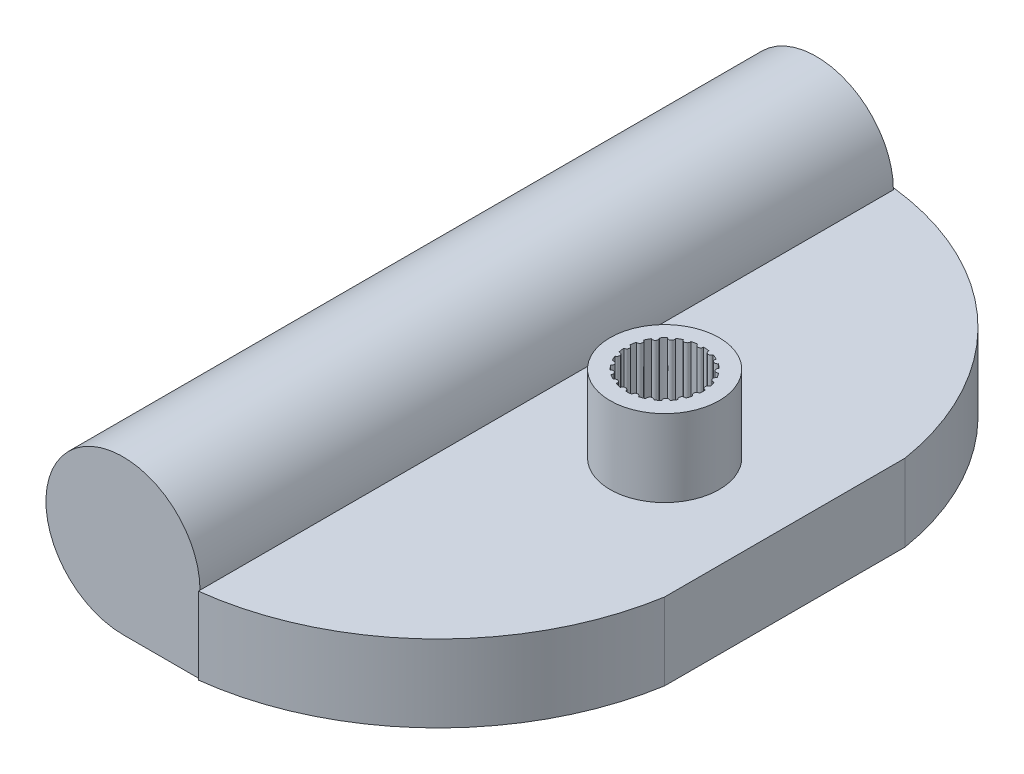
SolidWorks part; units mm, degrees
ref_plane "Front Plane" through (0, 0, 0) normal (0, 0, 1) x (1, 0, 0)
ref_plane "Top Plane" through (0, 0, 0) normal (0, 1, 0) x (1, 0, 0)
ref_plane "Right Plane" through (0, 0, 0) normal (1, 0, 0) x (0, 0, -1)
sketch "Sketch1" plane through (0, 0, 0) normal (0, 1, 0) x (1, 0, 0)
  line L16 (-29.0895, -2.019) -> (-29.0895, -7.019)
  line L53 (-9.0895, -27.019) -> (-4.0895, -27.019)
  line L54 (15.9105, -7.019) -> (15.9105, -2.019)
  line L55 (-4.0895, 17.981) -> (-9.0895, 17.981)
  line L56 (-4.0895, -7.019) -> (1.2138, -12.3223) construction
  line L57 (-4.0895, -27.019) -> (1.2138, -12.3223)
  line L58 (1.2138, -12.3223) -> (15.9105, -7.019)
  line L59 (-4.0895, -2.019) -> (1.2138, 3.2843) construction
  line L60 (-9.0895, -2.019) -> (-14.3928, 3.2843) construction
  line L61 (-9.0895, -7.019) -> (-14.3928, -12.3223) construction
  line L62 (-29.0895, -7.019) -> (-14.3928, -12.3223)
  line L63 (-9.0895, -27.019) -> (-14.3928, -12.3223)
  line L64 (-29.0895, -2.019) -> (-14.3928, 3.2843)
  line L65 (-14.3928, 3.2843) -> (-9.0895, 17.981)
  line L66 (-4.0895, 17.981) -> (1.2138, 3.2843)
  line L67 (1.2138, 3.2843) -> (15.9105, -2.019)
  circle A0 centre (-6.5895, -4.519) radius 1
  dimension "D1" = 20
  dimension "D2" = 20
  dimension "D3" = 20
  dimension "D4" = 20
  dimension "D5" = 7.5
extrude "Boss-Extrude7" add sketch "Sketch1" along normal blind 2.5 and the other way blind 2.5
sketch "Sketch2" plane through (0, 2.5, 0) normal (0, 1, 0) x (1, 0, 0)
  line L1 (-29.0895, -2.019) -> (-29.0895, -7.019) construction
  line L2 (-29.0895, -2.019) -> (-12.9815, -2.019) construction
  circle A0 centre (-25.0895, -4.519) radius 0.8
  dimension "D1" = 2.5
  dimension "D2" = 4
extrude "Cut-Extrude1" [suppressed] cut sketch "Sketch2" against normal blind 32.5 contours A0
pattern_linear "LPattern1" [suppressed] count 4 spacing 4 of bodies 104
pattern_circular "CirPattern1" [suppressed] count 4 over 360 of bodies 105
sketch "Sketch3" plane through (0, 2.5, 0) normal (0, 1, 0) x (1, 0, 0)
  line L1 (-9.0895, -7.019) -> (-4.0895, -7.019)
  line L2 (-9.0895, -7.019) -> (-9.0895, -2.019)
  line L3 (-9.0895, -2.019) -> (-4.0895, -2.019)
  line L4 (-4.0895, -7.019) -> (-4.0895, -2.019)
  line L5 (-9.0895, -7.019) -> (-4.0895, -2.019) construction
  line L6 (-9.0895, -2.019) -> (-4.0895, -7.019) construction
  circle A0 centre (-6.5895, -4.519) radius 1
  dimension "D1" = 5
  dimension "D2" = 5
extrude "Boss-Extrude9" add sketch "Sketch3" along normal blind 1
fillet "Fillet2" radius 2.5 4 edges at (-4.0895, 3, 7.019) (-4.0895, 3, 2.019) (-9.0895, 3, 7.019) (-9.0895, 3, 2.019)
sketch "Sketch4" plane through (0, 2.5, 0) normal (0, 1, 0) x (1, 0, 0)
  circle A1 centre (-6.5895, -4.519) radius 2.5
  circle A2 centre (-6.5895, -4.519) radius 3.54
extrude "Boss-Extrude11" add sketch "Sketch4" along normal blind 5
sketch "Sketch8" plane through (0, 7.5, 0) normal (0, 1, 0) x (1, 0, 0)
  line L0 (-6.5895, -4.519) -> (-7.2912, -2.1195) construction
  line L2 (-7.641, -2.2509) -> (-6.5895, -4.519) construction
  circle A0 centre (-6.5895, -4.519) radius 2.5
  arc A1 (-7.641, -2.2509) -> (-7.2912, -2.1195) centre (-7.471, -2.1721) ccw
  circle A2 centre (-6.5895, -4.519) radius 2.5 construction
  dimension "D1" = 8.571
extrude "Boss-Extrude13" add sketch "Sketch8" against normal up to surface (4 mm away) contours A1 region at (-7.4413, 7.5, 2.2513) up to face at (-6.5895, 3.5, 2.019)
pattern_circular "CirPattern2" count 21 over 360 about axis through (-6.5895, -2.5, 4.519) along (0, 1, 0) of "Boss-Extrude13"
sketch "Sketch18" plane through (0, 0, -17.981) normal (0, 0, -1) x (-1, 0, 0)
  line L1 (14.3928, 2.5) -> (14.3928, -2.5) construction
  line L2 (14.3928, 0) -> (14.3928, -2.5) construction
  circle A0 centre (19.2428, 2.5) radius 4.05
  circle A1 centre (19.2428, 2.5) radius 5
  dimension "D2" = 8.1
  dimension "D3" = 5
  dimension "D1" = 4.85
extrude "Boss-Extrude24" add sketch "Sketch18" against normal blind 45
sketch "Sketch19" plane through (0, 0, -17.981) normal (0, 0, -1) x (-1, 0, 0)
  circle A0 centre (19.2428, 2.5) radius 4.05
extrude "Cut-Extrude2" cut sketch "Sketch19" against normal through all
sketch "Sketch20" plane through (0, 0, 27.019) normal (0, 0, 1) x (1, 0, 0)
  circle A0 centre (-19.2428, 2.5) radius 5
extrude "Boss-Extrude25" add sketch "Sketch20" against normal blind 5
sketch "Sketch21" plane through (-2.7068, 0, -7.5012) normal (-0.3394, 0, -0.9406) x (-0.9406, 0, 0.3394)
sketch "Sketch24" plane through (0, 0, -17.981) normal (0, 0, -1) x (-1, 0, 0)
  line L0 (19.2428, -2.5) -> (29.2396, -2.5)
  line L1 (29.2396, -2.5) -> (29.2396, 2.5)
  line L2 (29.2396, 2.5) -> (24.2428, 2.5)
  arc A0 (24.2428, 2.5) -> (19.2428, -2.5) centre (19.2428, 2.5) cw
  circle A1 centre (19.2428, 2.5) radius 5 construction
extrude "Cut-Extrude4" cut sketch "Sketch24" against normal blind 45
sketch "Sketch26" plane through (0, 2.5, 0) normal (0, 1, 0) x (1, 0, 0)
  line L5 (-14.2428, 17.981) -> (-24.2428, 17.981) construction
  line L6 (1.2138, 3.2843) -> (1.2138, -12.3223)
  line L7 (1.2138, -12.3223) -> (15.9105, -7.019) construction
  line L8 (-24.2428, -27.019) -> (-14.2428, -27.019) construction
  line L9 (-19.2428, 17.981) -> (-19.2428, -27.019)
  arc A0 (-19.2428, 17.981) -> (1.2138, 3.2843) centre (-16.3629, 0.4043) cw
  arc A1 (1.2138, -12.3223) -> (-19.2428, -27.019) centre (-16.3629, -9.4424) cw
extrude "Boss-Extrude35" add sketch "Sketch26" against normal blind 5
sketch "Sketch28" plane through (0, 2.5, 0) normal (0, 1, 0) x (1, 0, 0)
  line L0 (-19.2428, 17.981) -> (-14.2919, 18.0946)
  line L1 (-14.2428, 17.981) -> (-24.2428, 17.981) construction
  line L2 (-19.2428, 17.981) -> (-19.2428, 20.1795)
  line L3 (-19.2428, 20.1795) -> (-14.2919, 20.1795)
  line L4 (-14.2919, 20.1795) -> (-14.2919, 18.0946)
  line L5 (-19.2428, -27.019) -> (-14.2428, -27.019)
  line L6 (-24.2428, -27.019) -> (-14.2428, -27.019) construction
  line L7 (-14.2428, -27.019) -> (-14.2428, -28.9191)
  line L8 (-14.2428, -28.9191) -> (-19.2428, -28.9191)
  line L9 (-19.2428, -28.9191) -> (-19.2428, -27.019)
  arc A0 (-9.5011, 16.8405) -> (-19.2428, 17.981) centre (-16.3629, 0.4043) ccw construction
extrude "Cut-Extrude9" cut sketch "Sketch28" against normal blind 45
sketch "Sketch30" plane through (0, 2.5, 0) normal (0, 1, 0) x (1, 0, 0)
  line L0 (-14.2428, 17.981) -> (-24.2428, 17.981) construction
  line L1 (1.2138, 3.2843) -> (1.2138, -12.3223)
  line L3 (-19.2428, -27.019) -> (-19.2428, -29.8755)
  line L4 (-19.2428, -29.8755) -> (19.2858, -29.8755)
  line L5 (19.2858, -29.8755) -> (19.2858, 19.7802)
  line L6 (19.2858, 19.7802) -> (-19.2428, 19.7802)
  line L7 (-19.2428, 19.7802) -> (-19.2428, 17.981)
  arc A0 (-19.2428, 17.981) -> (1.2138, 3.2843) centre (-16.3629, 0.4043) cw
  arc A1 (1.2138, -12.3223) -> (-19.2428, -27.019) centre (-16.3629, -9.4424) cw
extrude "Cut-Extrude10" cut sketch "Sketch30" against normal blind 45
sketch "Sketch32" plane through (0, 0, -17.981) normal (0, 0, -1) x (-1, 0, 0)
  circle A0 centre (19.2428, 2.5) radius 4.05
extrude "Cut-Extrude12" cut sketch "Sketch32" against normal blind 40 and the other way blind 40
sketch "Sketch33" plane through (0, 2.5, 0) normal (0, 1, 0) x (1, 0, 0)
  circle A1 centre (-6.5895, -4.519) radius 1
extrude "Cut-Extrude13" cut sketch "Sketch33" against normal blind 40
